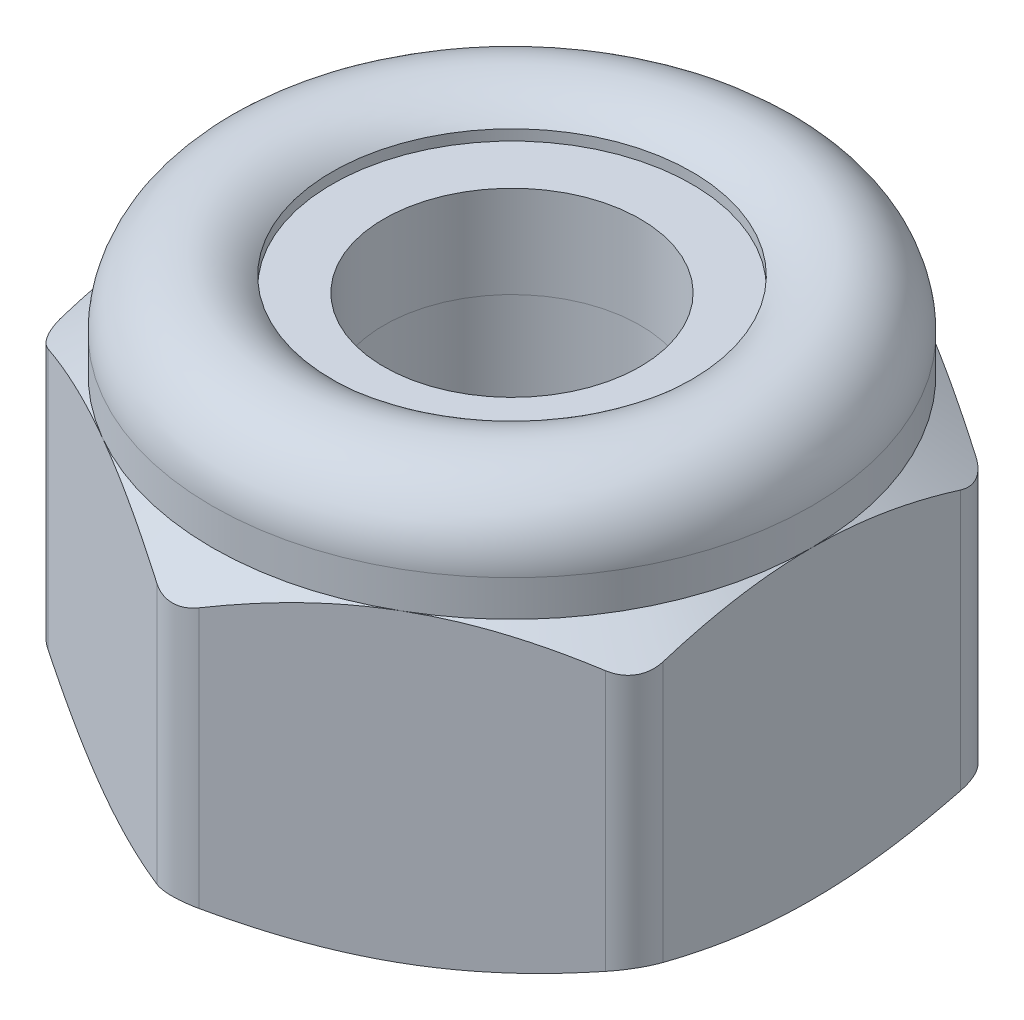
SolidWorks part; units mm, degrees
material "Alloy Steel"
ref_plane "Front Plane" through (0, 0, 0) normal (0, 0, 1) x (1, 0, 0)
ref_plane "Top Plane" through (0, 0, 0) normal (0, 1, 0) x (1, 0, 0)
ref_plane "Right Plane" through (0, 0, 0) normal (1, 0, 0) x (0, 0, -1)
sketch "Sketch1" plane through (0, 0, 0) normal (0, 0, 1) x (1, 0, 0)
  line L0 (0, -1.95) -> (0, 1.95) construction
  line L1 (2.75, 0) -> (-2.75, 0) construction
  line L2 (1.5, -1.95) -> (-1.5, -1.95) construction
  line L3 (1.5, -1.95) -> (1.5, -1.45) construction
  point P4 (0, 0)
  point P8 (0, 0)
  point P11 (0, -1.95)
  dimension "Height" = 3.9
  dimension "Width" = 5.5
  dimension "Thread Size" = 3
  dimension "Thread Pitch" = 0.5
sketch "Sketch2" plane through (0, 0, 0) normal (0, 1, 0) x (1, 0, 0)
  line L0 (-1.5, 0.2187) -> (-1.5, -0.2187) construction
  line L1 (0, 3.1754) -> (-2.75, 1.5877)
  line L2 (-2.75, 1.5877) -> (-2.75, -1.5877)
  line L3 (-2.75, -1.5877) -> (0, -3.1754)
  line L4 (0, -3.1754) -> (2.75, -1.5877)
  line L5 (2.75, -1.5877) -> (2.75, 1.5877)
  line L6 (2.75, 1.5877) -> (0, 3.1754)
  line L7 (-1.5, -0.2187) -> (-1.1752, -0.0313) construction
  line L8 (-1.1752, -0.0313) -> (-1.1752, 0.0312) construction
  line L9 (-1.1752, 0.0312) -> (-1.5, 0.2187) construction
  line L10 (-1.1752, 0) -> (-1.5, 0) construction
  line L11 (-1.3376, 0.125) -> (-1.3376, -0.125) construction
  line L12 (1.5, 0) -> (-1.5, 0) construction
  line L13 (2.75, 0) -> (-2.75, 0) construction
  circle A0 centre (0, 0) radius 2.75 construction
  circle A1 centre (0, 0) radius 1.1752
  point P19 (0, -1.1752)
  dimension "D1" = 0.0625
  dimension "D2" = 0.25
  dimension "D3" = 60
extrude "Boss-Extrude1" add sketch "Sketch2" along normal up to vertex (1.95 mm away) and the other way up to vertex (1.95 mm away) up to point (0, 1.95, 0) other way up to point (0, -1.95, 0)
fillet "Fillet1" radius 0.385 6 edges at (-2.75, 0, -1.5877) (0, 0, -3.1754) (-2.75, 0, 1.5877) (2.75, 0, -1.5877) (2.75, 0, 1.5877) (0, 0, 3.1754)
sketch "Sketch3" plane through (0, 0, 0) normal (1, 0, 0) x (0, 0, -1)
  line L0 (3.1754, 0.975) -> (3.1754, 2.95)
  line L1 (1.65, 0.78) -> (2.75, 0.78) construction
  line L2 (2.53, -1.95) -> (3.1754, -1.5774)
  line L3 (1.6989, -1.95) -> (3.0643, -1.95) construction
  line L4 (3.1754, 1.95) -> (3.1754, -1.95) construction
  line L5 (3.1754, -1.5774) -> (3.1754, -1.95)
  line L6 (3.1754, -1.95) -> (2.53, -1.95)
  line L7 (2.75, 0.975) -> (3.1754, 0.6771)
  line L8 (3.1754, 0.6771) -> (3.1754, 0.975)
  line L9 (2.75, 0.78) -> (2.75, 0.975) construction
  line L10 (1.6989, -1.95) -> (3.0643, -1.95) construction
  line L11 (2.75, 0.975) -> (2.75, 1.3056)
  line L12 (1.6989, 1.95) -> (3.0643, 1.95) construction
  line L13 (1.1752, 0.78) -> (1.65, 0.78)
  line L14 (1.65, 0.78) -> (1.65, 1.7613)
  line L16 (1.65, 1.7613) -> (2.1056, 1.3056) construction
  line L17 (2.1056, 1.3056) -> (2.1056, 1.95) construction
  line L18 (1.1752, 0.78) -> (1.1752, 2.95)
  line L19 (1.1752, 2.95) -> (3.1754, 2.95)
  line L21 (1.1752, -1.95) -> (1.1752, -1.65)
  line L22 (-1.3654, -1.95) -> (1.3654, -1.95) construction
  line L24 (1.4752, -1.95) -> (1.1752, -1.95)
  line L25 (1.1752, -1.65) -> (1.4752, -1.95)
  line L26 (0, 1.95) -> (0, -1.95) construction
  line L27 (-1.3654, 1.95) -> (1.3654, 1.95) construction
  line L28 (-1.3654, -1.95) -> (1.3654, -1.95) construction
  arc A0 (2.75, 1.3056) -> (1.65, 1.7613) centre (2.1056, 1.3056) ccw
  point P0 (2.75, 0.975)
  point P1 (2.75, 0)
  point P14 (1.1752, 0)
  point P36 (2.75, -1.95)
  dimension "D1" = 2.925
  dimension "D2" = 30
  dimension "D3" = 45
  dimension "D4" = 1
  dimension "D5" = 0.3
  dimension "D6" = 2.73
  dimension "D7" = 0.22
  dimension "D8" = 35
  dimension "D9" = 3.3
revolve "Cut-Revolve2" cut sketch "Sketch3" angle 360 about L0
sketch "Sketch12" plane through (0, 0, 0) normal (1, 0, 0) x (0, 0, -1)
  line L0 (2.1056, 1.3056) -> (2.1056, 1.95) construction
  line L1 (1.65, 0.78) -> (2.1056, 0.78)
  line L2 (1.65, 0.78) -> (1.65, 1.6638)
  line L3 (1.65, 1.6638) -> (2.1056, 1.6638)
  line L4 (2.1056, 0.78) -> (2.1056, 1.6638)
  dimension "D1" = 0.0975
revolve "Cut-Revolve3" cut sketch "Sketch12" angle 360 about L26
sketch "Sketch4" plane through (0, 0, 0) normal (1, 0, 0) x (0, 0, -1)
  line L1 (1.1752, 0.78) -> (2.1056, 0.78)
  line L2 (1.1752, 0.78) -> (1.1752, 1.6248)
  line L3 (1.1752, 1.6248) -> (2.1056, 1.6248)
  line L4 (2.1056, 0.78) -> (2.1056, 1.6248)
  line L5 (1.65, 1.7613) -> (-1.65, 1.7613) construction
  line L7 (2.1056, 1.3056) -> (2.1056, 1.95) construction
  dimension "D1" = 0.1365
revolve "Revolve1" add sketch "Sketch4" angle 360 about L0
sketch "Sketch5" plane through (0, 0, 0) normal (0, 1, 0) x (1, 0, 0)
  circle A0 centre (0, 0) radius 1.1752 construction
  point P0 (0, -1.1752)
sketch "Sketch6" [suppressed] plane through (0, 0, 0) normal (1, 0, 0) x (0, 0, -1)
  line L0 (1.4752, 0.78) -> (1.4752, -1.95)
  line L3 (1.4752, -1.95) -> (0, -1.95)
  line L4 (0, -1.95) -> (0, 0.78)
  line L5 (0, -1.95) -> (0, 1.95) construction
  line L6 (0, 0.78) -> (1.4752, 0.78)
  line L7 (-1.4752, -1.95) -> (1.4752, -1.95) construction
  line L9 (1.1752, 0.78) -> (1.65, 0.78) construction
revolve "Revolve2" [suppressed] add sketch "Sketch6" angle 360 about L4
sketch "Sketch7" [suppressed] plane through (0, -1.95, 0) normal (0, -1, 0) x (1, 0, 0)
  circle A2 centre (0, 0) radius 1.4752
  circle A3 centre (0, 0) radius 1.4752
  dimension "D1" = 0
curve "Helix/Spiral1" [suppressed] pitch 0.5 height 3.9 turns 7.8
sketch "Sketch8" [suppressed] plane through (0, 0, 0) normal (0, 0, 1) x (1, 0, 0)
  line L0 (1.5294, -1.9187) -> (1.0964, -2.1687) construction
  line L1 (1.0964, -2.1687) -> (1.5294, -2.4187) construction
  line L2 (1.5294, -2.4187) -> (1.5294, -1.9187) construction
  line L3 (1.1505, -2.1375) -> (1.1505, -2.2)
  line L4 (1.4752, -1.95) -> (1.4752, -2.3875) construction
  line L5 (1.4752, -2.1687) -> (1.5294, -2.1687) construction
  line L6 (1.0964, -2.1687) -> (1.1505, -2.1687) construction
  line L7 (1.5023, -2.1687) -> (1.5023, -2.4031) construction
  line L8 (1.1505, -2.1375) -> (1.5294, -1.9187)
  line L9 (1.5294, -1.9187) -> (1.5023, -2.4031)
  line L10 (1.1505, -2.2) -> (1.5023, -2.4031)
  dimension "D1" = 0.5
  dimension "D2" = 0.0625
sweep "Cut-Sweep1" [suppressed] cut profiles "Sketch8" path "Helix/Spiral1"
sketch "Sketch9" [suppressed] plane through (0, 0, 0) normal (0, 0, 1) x (1, 0, 0)
  line L5 (0, -0.45) -> (0, -1.95)
  line L6 (0, -1.95) -> (1.5, -1.95)
  line L7 (1.5, -1.95) -> (0, -0.45)
revolve "Revolve3" [suppressed] add sketch "Sketch9" angle 360 about L5
sketch "Sketch10" [suppressed] plane through (0, -1.95, 0) normal (0, -1, 0) x (1, 0, 0)
  circle A0 centre (0, 0) radius 1.4752 construction
  circle A1 centre (0, 0) radius 1.4752
extrude "Boss-Extrude2" [suppressed] add sketch "Sketch10" against normal up to surface (2.73 mm away)
combine bodies "Combine1" [suppressed] operation type add bodies to combine 110 109
equation "\"D1@Sketch3\"=\"Height@Sketch1\" *.75"
equation "\"D5@Sketch3\"=\"Thread Size@Sketch1\"*.1"
equation "\"D4@Helix/Spiral1\"=\"Thread Pitch@sketch1\""
equation "\"D3@Helix/Spiral1\"=\"Height@sketch1\""
equation "\"D1@Sketch8\"=\"Thread Pitch@sketch1\""
equation "\"D2@Sketch8\"=\"Thread Pitch@sketch1\"/8"
equation "\"D1@Sketch2\"=\"Thread Pitch@sketch1\"/8"
equation "\"D2@Sketch2\"=\"Thread Pitch@sketch1\"/2"
equation "\"D1@Sketch4\"=\"Height@Sketch1\" * .035"
equation "\"D1@Fillet1\"=\"Width@Sketch1\" * .07"
equation "\"D6@Sketch3\"=\"Height@Sketch1\" *.7"
equation "\"D7@Sketch3\"=\"Width@Sketch1\"*.04"
equation "\"D9@Sketch3\"=\"Thread Size@Sketch1\"*1.1"
equation "\"D1@Sketch12\"=\"Height@Sketch1\" * .025"
